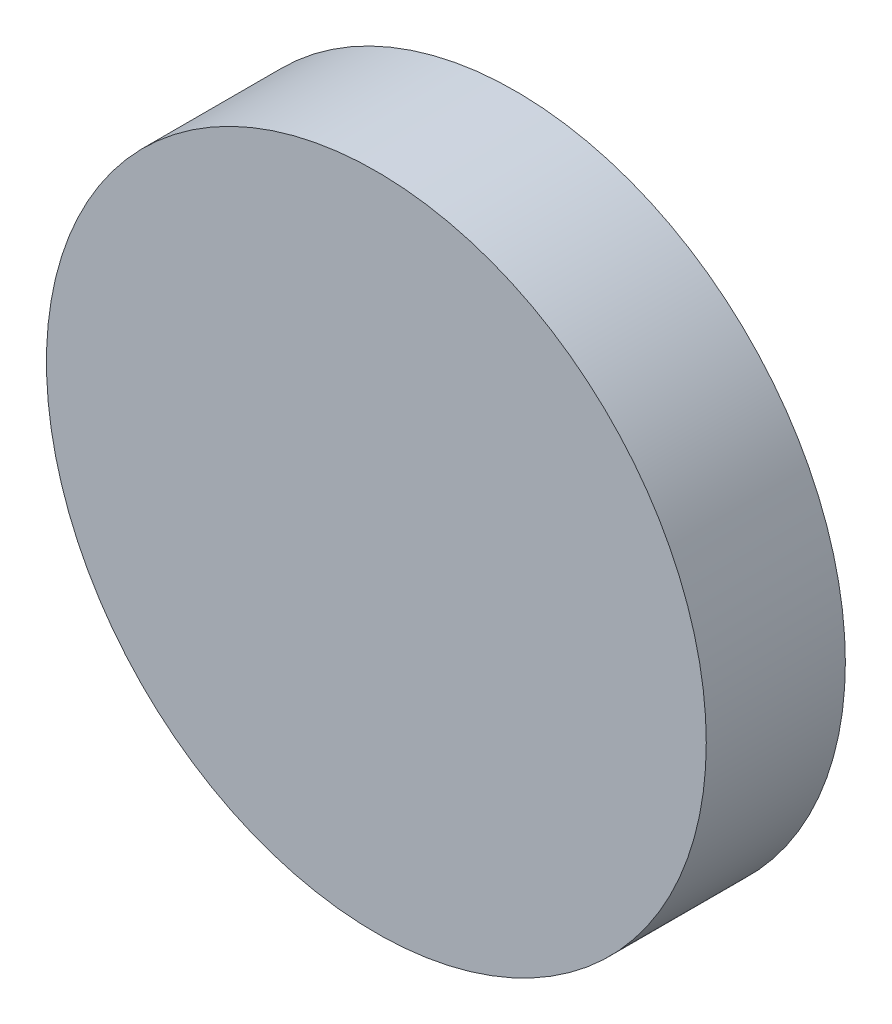
SolidWorks part; units mm, degrees
ref_plane "Front Plane" through (0, 0, 0) normal (0, 0, 1) x (1, 0, 0)
ref_plane "Top Plane" through (0, 0, 0) normal (0, 1, 0) x (1, 0, 0)
ref_plane "Right Plane" through (0, 0, 0) normal (1, 0, 0) x (0, 0, -1)
sketch "Sketch1" plane through (0, 0, 0) normal (0, 0, 1) x (1, 0, 0)
  line L0 (0, 0) -> (0, 17.78) construction
  line L1 (0, 17.78) -> (0, 20.32) construction
  line L2 (-4.2862, 20.275) -> (-4.2862, 22.4546)
  line L3 (4.9595, 17.78) -> (4.2862, 22.4546)
  line L8 (12.9182, -13.1851) -> (17.3031, -14.9393)
  line L9 (19.7017, -6.4255) -> (21.5894, -7.5153)
  line L12 (-17.8777, -4.5949) -> (-21.5894, -7.5153)
  line L13 (-15.4155, -13.8495) -> (-17.3031, -14.9393)
  line L14 (0, -55) -> (0, 55) construction
  circle A0 centre (0, 17.78) radius 1.778
  arc A1 (23.0969, 13.335) -> (11.6299, 24.0007) centre (0, 0) ccw
  arc A2 (-4.2862, 22.4546) -> (-19.7973, 11.43) centre (0, 0) ccw
  arc A3 (-4.2862, 20.275) -> (4.9595, 17.78) centre (0, 17.78) ccw
  arc A5 (19.7973, 11.43) -> (4.2862, 22.4546) centre (0, 0) ccw
  arc A6 (11.6299, -24.0007) -> (24.0007, -11.6299) centre (0, 0) ccw
  arc A7 (0, -22.86) -> (17.3031, -14.9393) centre (0, 0) ccw
  arc A8 (19.7017, -6.4255) -> (12.9182, -13.1851) centre (15.3979, -8.89) ccw
  arc A9 (21.5894, -7.5153) -> (19.7973, 11.43) centre (0, 0) ccw
  circle A10 centre (15.3979, -8.89) radius 1.778
  arc A11 (-23.0969, 13.335) -> (-24.0007, 11.6299) centre (0, 0) ccw
  arc A12 (-19.7973, 11.43) -> (-21.5894, -7.5153) centre (0, 0) ccw
  arc A13 (-15.4155, -13.8495) -> (-17.8777, -4.5949) centre (-15.3979, -8.89) ccw
  arc A14 (-17.3031, -14.9393) -> (0, -22.86) centre (0, 0) ccw
  circle A15 centre (-15.3979, -8.89) radius 1.778
  arc A16 (-14.5798, 28.0468) -> (14.5798, 28.0468) centre (0, 4.5835) cw
  arc A17 (12.9427, 26.3676) -> (14.5798, 28.0468) centre (13.7547, 27.2136) ccw
  arc A18 (-12.9427, 26.3676) -> (-14.5798, 28.0468) centre (-13.7547, 27.2136) cw
  arc A19 (-11.6299, 24.0007) -> (-23.0969, 13.335) centre (0, 0) ccw
  arc A20 (28.0468, 14.5798) -> (28.0468, -14.5798) centre (4.5835, 0) cw
  arc A21 (26.3676, -12.9427) -> (28.0468, -14.5798) centre (27.2136, -13.7547) ccw
  arc A22 (26.3676, 12.9427) -> (28.0468, 14.5798) centre (27.2136, 13.7547) cw
  arc A23 (14.5798, -28.0468) -> (-14.5798, -28.0468) centre (0, -4.5835) cw
  arc A24 (-12.9427, -26.3676) -> (-14.5798, -28.0468) centre (-13.7547, -27.2136) ccw
  arc A25 (12.9427, -26.3676) -> (14.5798, -28.0468) centre (13.7547, -27.2136) cw
  arc A26 (-28.0468, -14.5798) -> (-28.0468, 14.5798) centre (-4.5835, 0) cw
  arc A27 (-26.3676, 12.9427) -> (-28.0468, 14.5798) centre (-27.2136, 13.7547) ccw
  arc A28 (-26.3676, -12.9427) -> (-28.0468, -14.5798) centre (-27.2136, -13.7547) cw
  arc A29 (24.0007, 11.6299) -> (23.0969, 13.335) centre (0, 0) ccw
  arc A30 (-24.0007, -11.6299) -> (-11.6299, -24.0007) centre (0, 0) ccw
  spline S0 degree 3 poles (12.9427, 26.3676) (12.4899, 26.5244) (10.2146, 26.8236) (8.515, 25.8051) (11.6299, 24.0007) knots 0.119188 0.119188 0.119188 0.119188 0.354139 1 1 1 1
  spline S1 degree 3 poles (-12.9427, 26.3676) (-12.4899, 26.5244) (-10.2146, 26.8236) (-8.515, 25.8051) (-11.6299, 24.0007) knots 0.119188 0.119188 0.119188 0.119188 0.354139 1 1 1 1
  spline S2 degree 3 poles (26.3676, -12.9427) (26.5244, -12.4899) (26.8236, -10.2146) (25.8051, -8.515) (24.0007, -11.6299) knots 0.119188 0.119188 0.119188 0.119188 0.354139 1 1 1 1
  spline S3 degree 3 poles (26.3676, 12.9427) (26.5244, 12.4899) (26.8236, 10.2146) (25.8051, 8.515) (24.0007, 11.6299) knots 0.119188 0.119188 0.119188 0.119188 0.354139 1 1 1 1
  spline S4 degree 3 poles (-12.9427, -26.3676) (-12.4899, -26.5244) (-10.2146, -26.8236) (-8.515, -25.8051) (-11.6299, -24.0007) knots 0.119188 0.119188 0.119188 0.119188 0.354139 1 1 1 1
  spline S5 degree 3 poles (12.9427, -26.3676) (12.4899, -26.5244) (10.2146, -26.8236) (8.515, -25.8051) (11.6299, -24.0007) knots 0.119188 0.119188 0.119188 0.119188 0.354139 1 1 1 1
  spline S6 degree 3 poles (-26.3676, 12.9427) (-26.5244, 12.4899) (-26.8236, 10.2146) (-25.8051, 8.515) (-24.0007, 11.6299) knots 0.119188 0.119188 0.119188 0.119188 0.354139 1 1 1 1
  spline S7 degree 3 poles (-26.3676, -12.9427) (-26.5244, -12.4899) (-26.8236, -10.2146) (-25.8051, -8.515) (-24.0007, -11.6299) knots 0.119188 0.119188 0.119188 0.119188 0.354139 1 1 1 1
  point P6 (0, 19.05)
  point P37 (0, 0)
  point P86 (0, 0)
  dimension "D1" = 17.78
  dimension "D2" = 3.556
  dimension "D3" = 53.34
  dimension "D4" = 45.72
  dimension "D5" = 4
  dimension "D7" = 3
extrude "Boss-Extrude1" add sketch "Sketch1" along normal mid plane 5.08
fillet "Fillet1" radius 2.54 6 edges at (21.5894, -7.5153, 0) (17.3031, -14.9393, 0) (-17.3031, -14.9393, 0) (-21.5894, -7.5153, 0) (-4.2863, 22.4546, 0) (4.2862, 22.4546, 0)
sketch "Sketch3" plane through (0, 0, 2.54) normal (0, 0, 1) x (1, 0, 0)
  circle A0 centre (0, 0) radius 32.2077
  arc A5 (-28.0468, 14.5798) -> (-28.0468, -14.5798) centre (-4.5835, 0) ccw construction
  circle A7 centre (0, 17.78) radius 1.778
  circle A8 centre (-15.3979, -8.89) radius 1.778
  circle A9 centre (15.3979, -8.89) radius 1.778
  circle A10 centre (0, 0) radius 38.5577
  circle A11 centre (0, 0) radius 42.1736
  circle M3 centre (15.3979, -8.89) radius 1.778
  circle M28 centre (0, 17.78) radius 1.778
  circle M44 centre (-15.3979, -8.89) radius 1.778
  dimension "D1" = 6.35
extrude "Boss-Extrude2" add sketch "Sketch3" against normal blind 15.24 contours A11 A10 | M28 | M44 | M3 region at (0, 17.78, 2.54) region at (-15.3979, -8.89, 2.54) region at (15.3979, -8.89, 2.54) region at (-40.9808, 0, 2.54)
sketch "Sketch4" plane through (0, 0, 2.54) normal (0, 0, 1) x (1, 0, 0)
  circle A0 centre (0, 0) radius 42.1736
extrude "Boss-Extrude3" add sketch "Sketch4" along normal blind 2.54
